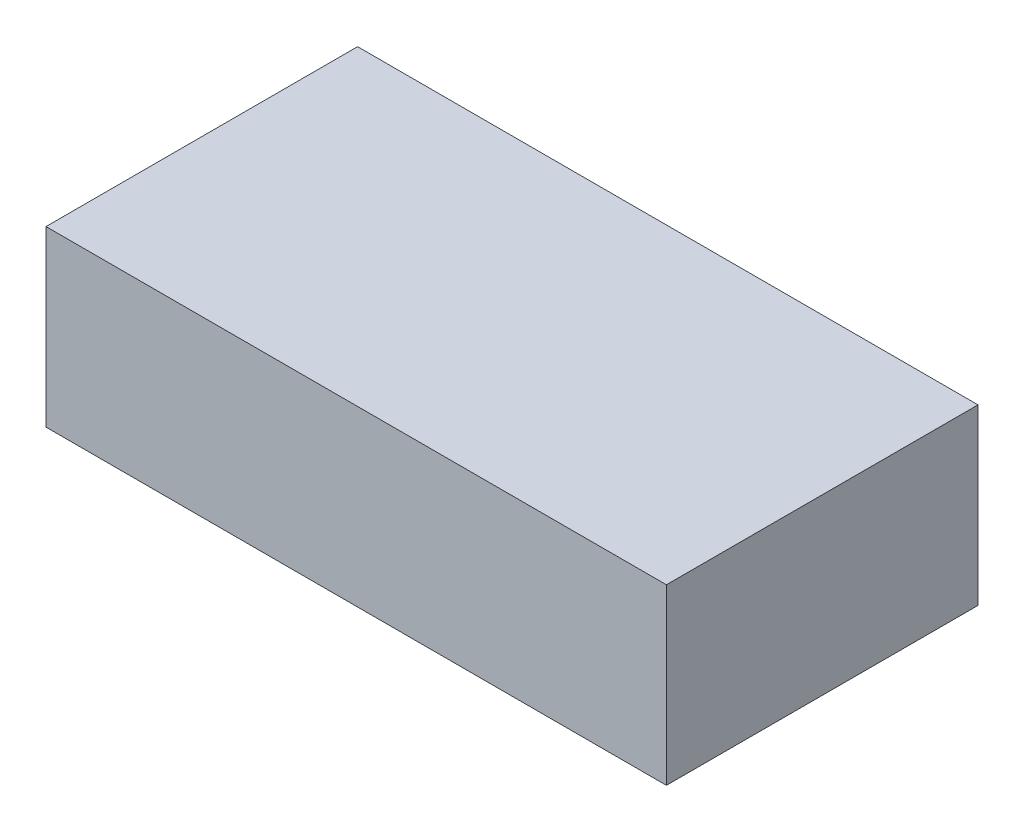
SolidWorks part; units mm, degrees
material "Стекло"
ref_plane "Спереди" through (0, 0, 0) normal (0, 0, 1) x (1, 0, 0)
ref_plane "Сверху" through (0, 0, 0) normal (0, 1, 0) x (1, 0, 0)
ref_plane "Справа" through (0, 0, 0) normal (1, 0, 0) x (0, 0, -1)
sketch "Эскиз1" plane through (0, 0, 0) normal (0, 1, 0) x (1, 0, 0)
  line L1 (112.5, -56.5) -> (-112.5, -56.5)
  line L2 (112.5, -56.5) -> (112.5, 56.5)
  line L3 (112.5, 56.5) -> (-112.5, 56.5)
  line L4 (-112.5, -56.5) -> (-112.5, 56.5)
  line L5 (112.5, -56.5) -> (-112.5, 56.5) construction
  line L6 (112.5, 56.5) -> (-112.5, -56.5) construction
  point P0 (0, 0)
  dimension "D1" = 225
  dimension "D2" = 113
extrude "Бобышка-Вытянуть1" add sketch "Эскиз1" along normal blind 63
